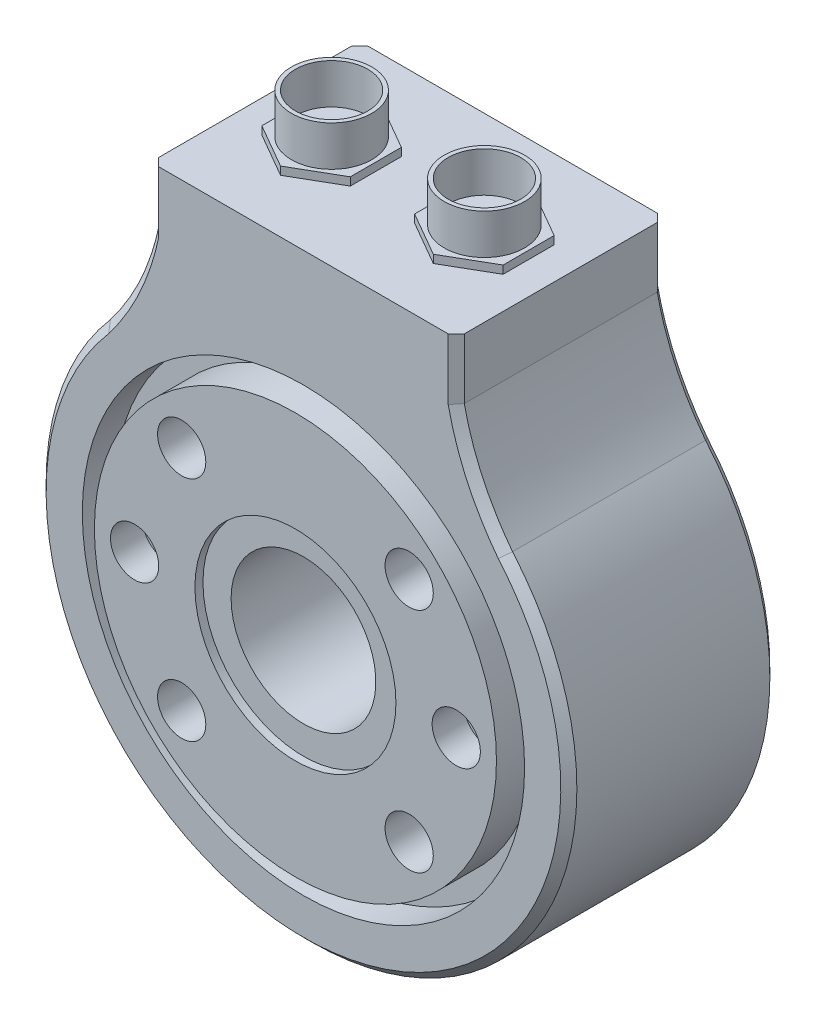
SolidWorks part; units mm, degrees
material "2014-O"
ref_plane "Front Plane" through (0, 0, 0) normal (0, 0, 1) x (1, 0, 0)
ref_plane "Top Plane" through (0, 0, 0) normal (0, 1, 0) x (1, 0, 0)
ref_plane "Right Plane" through (0, 0, 0) normal (1, 0, 0) x (0, 0, -1)
sketch "Sketch1" plane through (0, 0, 0) normal (0, 0, 1) x (1, 0, 0)
  line L0 (-19, 42) -> (19, 42)
  line L1 (-19, 42) -> (-19, 26.9815)
  line L2 (19, 42) -> (19, 26.9815)
  line L3 (0, 42) -> (0, 33)
  line L4 (0, 0) -> (0, 42) construction
  circle A0 centre (0, 0) radius 33
  circle A1 centre (0, 0) radius 9
  spline S0 degree 2 poles (-19, 34.4907) (-20.533, 27.3858) (-25, 21.5407) knots 0 0 0 1 1 1
  spline S1 degree 2 poles (19, 34.4907) (20.533, 27.3858) (25, 21.5407) knots 0 0 0 1 1 1
  point P10 (-20.5539, 28.6525)
  point P13 (-20.5539, 29.2855)
  dimension "D1" = 66
  dimension "D3" = 18
  dimension "D2" = 42
  dimension "38" = 38
  dimension "D4" = 1.5539
  dimension "D5" = 7.8197
  dimension "D6" = 6
extrude "Boss-Extrude1" add sketch "Sketch1" along normal blind 26 contours A1 A0 | A0 L2 L0 L3 | A0 L3 L0 L1 | S1 L2 A0 | L1 S0 A0 region at (-10.3536, 36.3938, 0) region at (10.3536, 36.3938, 0) region at (-20.4993, 27.8796, 0) region at (9.6834, 30.5696, 0) region at (20.4993, 27.8796, 0)
sketch "Sketch2" plane through (0, 0, 0) normal (0, 0, -1) x (-1, 0, 0)
  line L0 (0, 0) -> (0, 25) construction
  line L1 (0, 0) -> (-25, 0) construction
  circle A0 centre (0, 0) radius 25
  circle A1 centre (0, 0) radius 12.5
  circle A2 centre (-20, 0) radius 3
  circle A3 centre (0, 0) radius 20
  circle A4 centre (0, 20) radius 2
  circle A5 centre (-14.1403, 14.1439) radius 2.5
  circle A6 centre (14.1403, 14.1439) radius 2.5
  circle A7 centre (20, 0) radius 3
  circle A8 centre (14.1403, -14.1439) radius 2.5
  circle A9 centre (0, -20) radius 2
  circle A10 centre (-14.1403, -14.1439) radius 2.5
  circle M9 centre (0, 0) radius 9
  dimension "D1" = 50
  dimension "D2" = 25
  dimension "D3" = 6
  dimension "D5" = 4
  dimension "D8" = 5
  dimension "D9" = 5
  dimension "D4" = 20
  dimension "D6" = 15.305
  dimension "D7" = 15.3097
  dimension "D10" = 15.305
extrude "Boss-Extrude2" add sketch "Sketch2" along normal blind 0.1 contours A0 A3 A10 A2 A5 A4 A6 A7 A8 A9 | A3 A10 A9 A8 A7 A6 A4 A5 A2 A1 region at (24.2929, 0, 0) region at (17.3892, 2.4218, 0)
extrude "Cut-Extrude1" cut sketch "Sketch2<5>" against normal blind 2 contours A1 M9 region at (12.1464, 0, 0)
sketch "Sketch2<5>" plane through (0, 0, 0) normal (0, 0, -1) x (-1, 0, 0) same geometry as "Sketch2"
extrude "Cut-Extrude2" cut sketch "Sketch2<6>" against normal blind 6 contours A3 A5 | A3 A5 | A6 | A8 | A10 region at (14.8703, 14.874, 0) region at (13.3706, 13.374, 0)
sketch "Sketch2<6>" plane through (0, 0, 0) normal (0, 0, -1) x (-1, 0, 0) same geometry as "Sketch2"
extrude "Cut-Extrude3" cut sketch "Sketch2<7>" against normal blind 5 contours A2 | A7
sketch "Sketch2<7>" plane through (0, 0, 0) normal (0, 0, -1) x (-1, 0, 0) same geometry as "Sketch2"
extrude "Cut-Extrude4" cut sketch "Sketch2<8>" against normal blind 4 contours A4 | A9
sketch "Sketch2<8>" plane through (0, 0, 0) normal (0, 0, -1) x (-1, 0, 0) same geometry as "Sketch2"
chamfer "Chamfer1" distance 1 angle 45 10 edges at (19, 38.2454, 26) (-19, 38.2454, 26) (0, -33, 26) (19, 38.2454, 0) (-19, 38.2454, 0) (0, -33, 0)
sketch "Sketch4" plane through (0, 0, 26) normal (0, 0, 1) x (1, 0, 0)
  line L0 (0, 0) -> (0, 27.5) construction
  line L1 (0, 0) -> (-20, 0) construction
  circle A0 centre (0, 0) radius 12.5
  circle A1 centre (0, 0) radius 25
  circle A2 centre (0, 0) radius 27.5
  circle A3 centre (0, 0) radius 9 construction
  circle A4 centre (0, 0) radius 9
  circle A5 centre (0, 0) radius 20
  circle A6 centre (-20, 0) radius 3
  circle A7 centre (-14.1439, 14.1403) radius 3
  circle A9 centre (-14.1439, -14.1403) radius 3
  circle A10 centre (14.1439, 14.1403) radius 3
  circle A11 centre (14.1439, -14.1403) radius 3
  circle A12 centre (20, 0) radius 3
  dimension "D1" = 25
  dimension "D2" = 50
  dimension "D3" = 55
  dimension "D4" = 40
  dimension "D5" = 6
  dimension "D6" = 6
  dimension "1" = 15.305
extrude "Boss-Extrude3" add sketch "Sketch4" along normal blind 1 contours A1 A5 A12 A11 A9 A6 A7 A10 | A5 A12 A10 A7 A6 A9 A11 A0 region at (-24.2929, 0, 26) region at (16.4375, 0, 26)
extrude "Cut-Extrude5" cut sketch "Sketch4<4>" against normal blind 4 contours A2 A1 region at (-26.7222, 0, 26)
sketch "Sketch4<4>" plane through (0, 0, 26) normal (0, 0, 1) x (1, 0, 0) same geometry as "Sketch4"
extrude "Cut-Extrude6" cut sketch "Sketch4<5>" against normal blind 3 contours A6 | A12
sketch "Sketch4<5>" plane through (0, 0, 26) normal (0, 0, 1) x (1, 0, 0) same geometry as "Sketch4"
extrude "Cut-Extrude7" cut sketch "Sketch4<6>" against normal blind 5 contours A10 | A7 | A9 | A11
sketch "Sketch4<6>" plane through (0, 0, 26) normal (0, 0, 1) x (1, 0, 0) same geometry as "Sketch4"
sketch "Sketch5" plane through (0, 42, 0) normal (0, 1, 0) x (1, 0, 0)
  line L0 (0, 0) -> (0, -26) construction
  line L1 (-18, 0) -> (18, 0) construction
  line L2 (-18, -26) -> (18, -26) construction
  line L3 (0, -13) -> (-19, -13) construction
  line L4 (-19, -25) -> (-19, -1) construction
  line L5 (0, -13) -> (19, -13) construction
  line L6 (19, -25) -> (19, -1) construction
  line L7 (-4, -16.1754) -> (-9.5, -19.3509)
  line L8 (9.5, -6.6491) -> (4, -9.8246)
  line L9 (4, -9.8246) -> (4, -16.1754)
  line L10 (4, -16.1754) -> (9.5, -19.3509)
  line L11 (9.5, -19.3509) -> (15, -16.1754)
  line L12 (15, -16.1754) -> (15, -9.8246)
  line L13 (15, -9.8246) -> (9.5, -6.6491)
  line L14 (-9.5, -19.3509) -> (-15, -16.1754)
  line L15 (-15, -16.1754) -> (-15, -9.8246)
  line L16 (-15, -9.8246) -> (-9.5, -6.6491)
  line L17 (-9.5, -6.6491) -> (-4, -9.8246)
  line L18 (-4, -9.8246) -> (-4, -16.1754)
  circle A1 centre (9.5, -13) radius 5.5 construction
  circle A2 centre (9.5, -13) radius 5
  circle A3 centre (-9.5, -13) radius 5
  circle A4 centre (9.5, -13) radius 4.5
  circle A5 centre (-9.5, -13) radius 4.5
  dimension "D3" = 10
  dimension "D4" = 9
  dimension "D1" = 11
  dimension "D2" = 4
extrude "Boss-Extrude4" add sketch "Sketch5" along normal blind 1 contours L10 L11 L12 L13 L8 L9 | L7 L14 L15 L16 L17 L18
extrude "Boss-Extrude5" add sketch "Sketch5<3>" along normal blind 6 contours A2 | A4 | A3 | A5
sketch "Sketch5<3>" plane through (0, 42, 0) normal (0, 1, 0) x (1, 0, 0) same geometry as "Sketch5"
